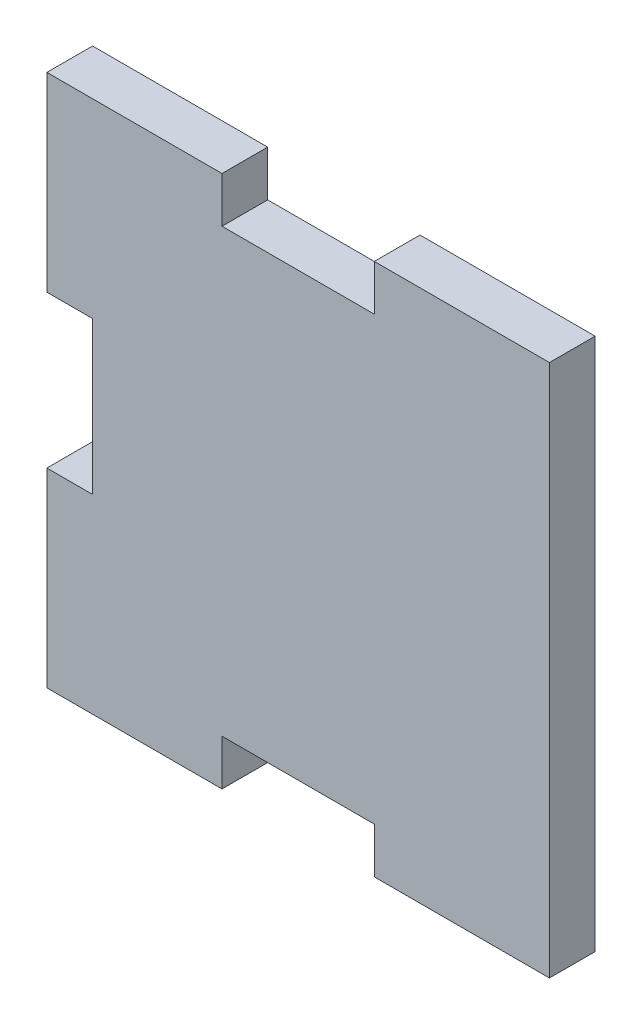
SolidWorks part; units mm, degrees
material "MDF"
ref_plane "Plano frontal" through (0, 0, 0) normal (0, 0, 1) x (1, 0, 0)
ref_plane "Plano superior" through (0, 0, 0) normal (0, 1, 0) x (1, 0, 0)
ref_plane "Plano direito" through (0, 0, 0) normal (1, 0, 0) x (0, 0, -1)
sketch "Esboço1" plane through (0, 0, 0) normal (0, 0, 1) x (1, 0, 0)
  line L0 (-16.5, 0) -> (16.5, 0) construction
  line L1 (-16.5, -17.5) -> (16.5, -17.5)
  line L2 (-16.5, -17.5) -> (-16.5, 17.5)
  line L3 (-16.5, 17.5) -> (16.5, 17.5)
  line L4 (16.5, -17.5) -> (16.5, 17.5)
  line L5 (-16.5, -17.5) -> (16.5, 17.5) construction
  line L6 (-16.5, 17.5) -> (16.5, -17.5) construction
  line L7 (5, 14.5) -> (-5, 14.5)
  line L8 (5, 14.5) -> (5, 17.5)
  line L9 (5, 17.5) -> (-5, 17.5)
  line L10 (-5, 14.5) -> (-5, 17.5)
  line L11 (5, 14.5) -> (-5, 17.5) construction
  line L12 (5, 17.5) -> (-5, 14.5) construction
  line L13 (5, -17.5) -> (-5, -17.5)
  line L14 (-5, -14.5) -> (-5, -17.5)
  line L15 (5, -14.5) -> (-5, -14.5)
  line L16 (5, -14.5) -> (5, -17.5)
  line L17 (-16.5, 5) -> (-13.5, 5)
  line L18 (-13.5, 5) -> (-13.5, -5)
  line L19 (-13.5, -5) -> (-16.5, -5)
  line L20 (-16.5, -5) -> (-16.5, 5)
  point P0 (0, 0)
  point P6 (0, 16)
  point P13 (0, 0)
  point P14 (0, 16)
  point P15 (0, 0)
  point P20 (-13.5, 0)
  point P28 (16.5, 0)
  dimension "D5" = 3
  dimension "D1" = 35
  dimension "D2" = 10
  dimension "D3" = 10
  dimension "D4" = 3
  dimension "D8" = 11.5
extrude "Ressalto-extrusão1" add sketch "Esboço1" along normal blind 3 contours L15 L16 L1 L4 L3 L8 L7 L10 L2 L14 region at (0.4225, 0, 0)
